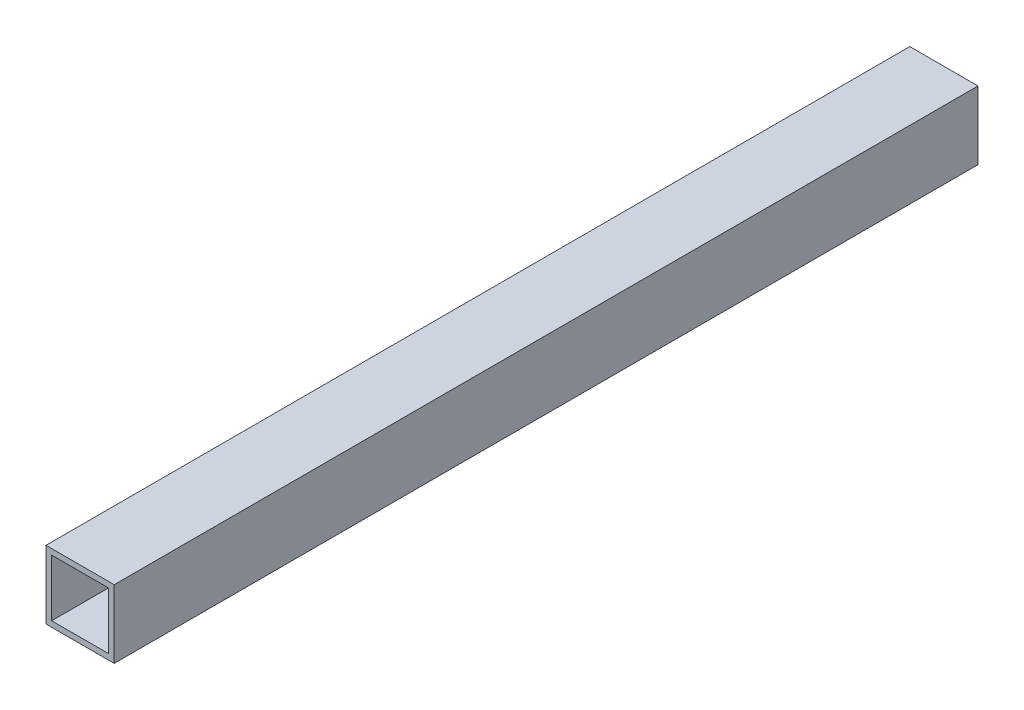
SolidWorks part; units mm, degrees
material "6061 Alloy"
ref_plane "Front Plane" through (0, 0, 0) normal (0, 0, 1) x (1, 0, 0)
ref_plane "Top Plane" through (0, 0, 0) normal (0, 1, 0) x (1, 0, 0)
ref_plane "Right Plane" through (0, 0, 0) normal (1, 0, 0) x (0, 0, -1)
sketch "Sketch2" plane through (0, 0, 0) normal (0, 0, 1) x (1, 0, 0)
  line L1 (-15.875, 15.875) -> (15.875, 15.875)
  line L2 (-15.875, 15.875) -> (-15.875, -15.875)
  line L3 (-15.875, -15.875) -> (15.875, -15.875)
  line L4 (15.875, 15.875) -> (15.875, -15.875)
  line L5 (-15.875, 15.875) -> (15.875, -15.875) construction
  line L6 (-15.875, -15.875) -> (15.875, 15.875) construction
  line L7 (-19.05, 19.05) -> (19.05, 19.05)
  line L8 (-19.05, 19.05) -> (-19.05, -19.05)
  line L9 (-19.05, -19.05) -> (19.05, -19.05)
  line L10 (19.05, 19.05) -> (19.05, -19.05)
  line L11 (-19.05, 19.05) -> (19.05, -19.05) construction
  line L12 (-19.05, -19.05) -> (19.05, 19.05) construction
  point P0 (0, 0)
  point P6 (0, 0)
  dimension "D1" = 38.1
  dimension "D2" = 38.1
  dimension "D3" = 3.175
  dimension "D4" = 3.175
extrude "Boss-Extrude1" add sketch "Sketch2" along normal blind 482.6
sketch "Sketch3" plane through (0, 0, 0) normal (1, 0, 0) x (0, 0, -1)
  line L0 (-477.1762, 0) -> (16.7996, 0) construction
